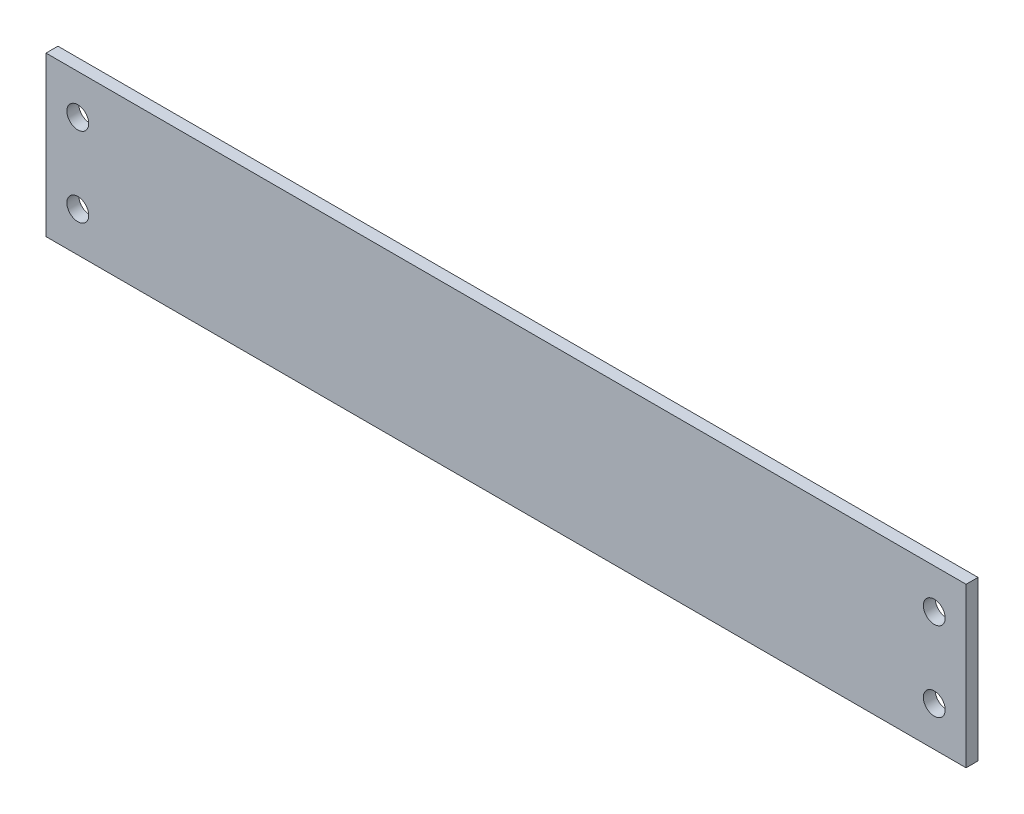
SolidWorks part; units mm, degrees
ref_plane "Front Plane" through (0, 0, 0) normal (0, 0, 1) x (1, 0, 0)
ref_plane "Top Plane" through (0, 0, 0) normal (0, 1, 0) x (1, 0, 0)
ref_plane "Right Plane" through (0, 0, 0) normal (1, 0, 0) x (0, 0, -1)
sketch "Extrusion Base Sketch" plane through (0, 0, 0) normal (0, 0, 1) x (1, 0, 0)
  line L0 (209.5, 36.75) -> (209.5, -3.25)
  line L1 (0, 0) -> (187.5, 0) construction
  line L2 (0, 0) -> (0, 33.5) construction
  line L3 (0, 33.5) -> (187.5, 33.5) construction
  line L4 (187.5, 0) -> (187.5, 33.5) construction
  line L5 (-22, 36.75) -> (209.5, 36.75)
  line L6 (-3.25, 36.75) -> (-3.25, -3.25) construction
  line L7 (-22, -3.25) -> (209.5, -3.25)
  line L8 (190.75, 36.75) -> (190.75, -3.25) construction
  line L9 (-22, 36.75) -> (-22, -3.25)
  line L10 (201.5, 26.75) -> (201.5, 6.75) construction
  line L11 (201.5, 16.75) -> (209.5, 16.75) construction
  line L12 (-14, 26.75) -> (-14, 6.75) construction
  point P9 (0, 0)
  point P10 (0, 0)
  dimension "D1" = 33.5
  dimension "D2" = 187.5
  dimension "D4" = 3.25
  dimension "D5" = 3.25
  dimension "D6" = 3.25
  dimension "D3" = 40
extrude "Extrusion Base Extrude" add sketch "Extrusion Base Sketch" against normal blind 3
hole_wizard "M5 Mounting Holes" positions "M5 Mounting Holes Position Sketch" profile "M5 Mounting Holes Profile Sketch" hole size "M5" standard "ANSI Metric" end condition through all
sketch "M5 Mounting Holes Position Sketch" plane through (0, 0, -3) normal (0, 0, -1) x (-1, 0, 0)
  point P0 (-201.5, 26.75)
  point P2 (-201.5, 6.75)
  point P4 (14, 26.75)
  point P6 (14, 6.75)
  point P9 (0, 0)
  point P11 (0, 0)
  point P13 (0, 0)
  point P15 (0, 0)
sketch "M5 Mounting Holes Profile Sketch" plane through (201.5, 26.75, -3) normal (1, 0, 0) x (0, 1, 0)
  line L0 (0, 0) -> (0, 3)
  line L1 (0, 3) -> (2.75, 3)
  line L2 (2.75, 3) -> (2.75, 0)
  line L5 (2.75, 0) -> (0, 0)
  line L11 (0, -6.35) -> (0, 107.95) construction
  dimension "Thru Hole Dia." = 5.5
  dimension "Thru Hole Depth" = 3
equation "\"Logo Height\"= 33.5mm"
equation "\"Total Height\"= 40mm"
equation "\"Border\"= ( \"Total Height\" - \"Logo Height\" ) / 2"
equation "\"Logo Length\"= 187.5mm"
equation "\"D1@Extrusion Base Sketch\" = \"Logo Height\""
equation "\"D2@Extrusion Base Sketch\" = \"Logo Length\""
equation "\"D4@Extrusion Base Sketch\" = \"Border\""
equation "\"D5@Extrusion Base Sketch\" = \"Border\""
equation "\"D6@Extrusion Base Sketch\" = \"Border\""
equation "\"D3@Extrusion Base Sketch\" = \"Total Height\""
